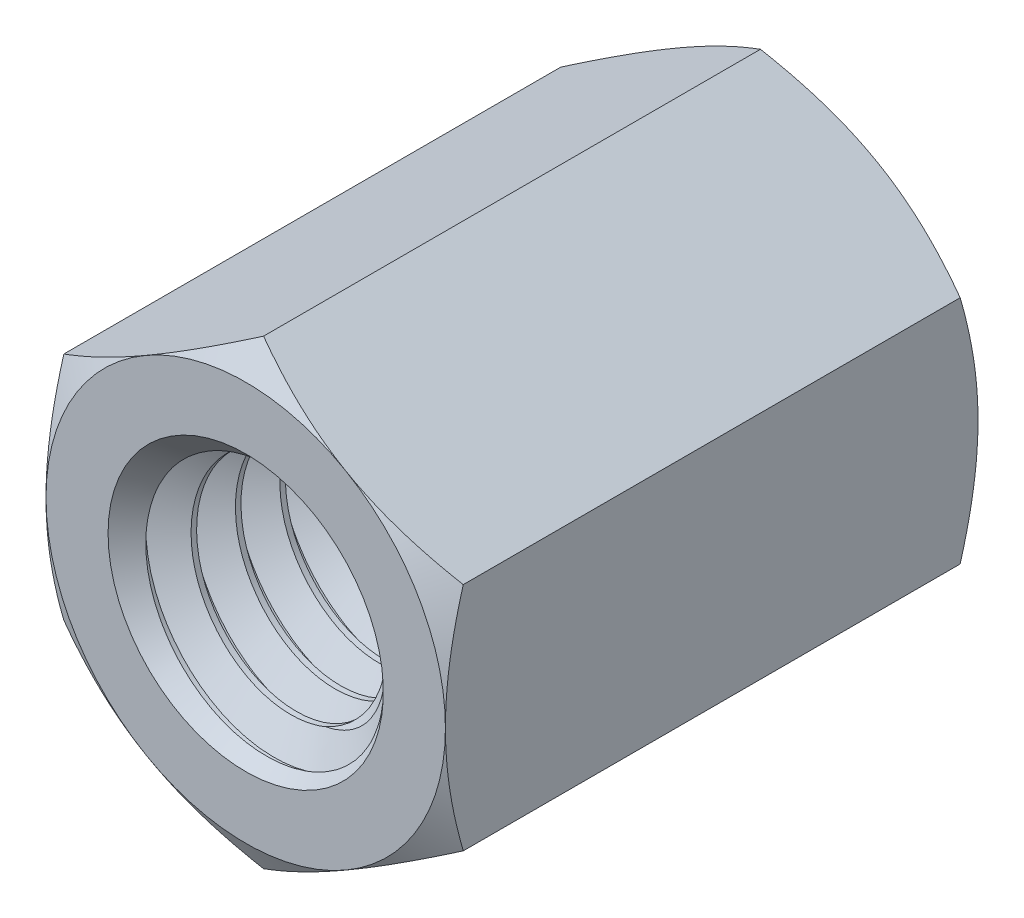
SolidWorks part; units mm, degrees
ref_plane "Front Plane" through (0, 0, 0) normal (0, 0, 1) x (1, 0, 0)
ref_plane "Top Plane" through (0, 0, 0) normal (0, 1, 0) x (1, 0, 0)
ref_plane "Right Plane" through (0, 0, 0) normal (1, 0, 0) x (0, 0, -1)
sketch "Sketch3" plane through (0, 0, 0) normal (1, 0, 0) x (0, 0, -1)
  line L0 (-3, 0) -> (3, 0) construction
  line L1 (0, 2.25) -> (0, -2.25) construction
  line L2 (-3, 1.5) -> (-3, -1.5) construction
  point P2 (-1.8, 0)
  point P3 (1.8, 0)
  dimension "Length" = 6
  dimension "Min Thread Length" = 4.8
  dimension "D1" = 4.8
  dimension "Thread Dia" = 3
  dimension "Hex" = 4.5
sketch "Sketch1" plane through (0, 0, 0) normal (0, 0, 1) x (1, 0, 0)
  line L1 (0, 2.5981) -> (-2.25, 1.299)
  line L2 (-2.25, 1.299) -> (-2.25, -1.299)
  line L3 (-2.25, -1.299) -> (0, -2.5981)
  line L4 (0, -2.5981) -> (2.25, -1.299)
  line L5 (2.25, -1.299) -> (2.25, 1.299)
  line L6 (2.25, 1.299) -> (0, 2.5981)
  circle A0 centre (0, 0) radius 2.25 construction
  circle A1 centre (0, 0) radius 1.5
extrude "Extrude1" add sketch "Sketch1" along normal up to vertex (3 mm away) and the other way up to vertex (3 mm away) up to point (0, 0, 3) other way up to point (0, 0, -3)
sketch "Sketch11" plane through (0, 0, -3) normal (0, 0, -1) x (-1, 0, 0)
  circle A0 centre (0, 0) radius 1.5 construction
  circle A1 centre (0, 0) radius 1.5
curve "Helix/Spiral1" pitch 0.5 height 6.5 radius 1.5 centre (0, 0, -3) axis (0, 0, 1) start towards (0, 1, 0) parameters "Pitch"=0.5
sketch "Sketch12" plane through (0, 0, 0) normal (1, 0, 0) x (0, 0, -1)
  line L0 (3.4375, 1.5) -> (3, 1.5)
  line L1 (3.4375, 1.5) -> (3.25, 1.1752)
  line L2 (3.25, 1.1752) -> (3.1875, 1.1752)
  line L3 (3.1875, 1.1752) -> (3, 1.5)
  line L4 (3.2187, 1.1752) -> (3.2187, 1.5) construction
  line L5 (3.3438, 1.3376) -> (3.0938, 1.3376) construction
  dimension "D1" = 0.0625
  dimension "D2" = 0.25
  dimension "D3" = 60
sweep "Sweep1" add profiles "Sketch12" path "Helix/Spiral1"
sketch "Sketch6" plane through (0, 0, -3) normal (0, 0, -1) x (-1, 0, 0)
  line L6 (0, 2.5981) -> (-2.25, 1.299)
  line L7 (-2.25, 1.299) -> (-2.25, -1.299)
  line L8 (-2.25, -1.299) -> (0, -2.5981)
  line L9 (0, -2.5981) -> (2.25, -1.299)
  line L10 (2.25, -1.299) -> (2.25, 1.299)
  line L11 (2.25, 1.299) -> (0, 2.5981)
  line L12 (0, 2.5981) -> (-2.25, 1.299)
  line L13 (-2.25, 1.299) -> (-2.25, -1.299)
  line L14 (-2.25, -1.299) -> (0, -2.5981)
  line L15 (0, -2.5981) -> (2.25, -1.299)
  line L16 (2.25, -1.299) -> (2.25, 1.299)
  line L17 (2.25, 1.299) -> (0, 2.5981)
  dimension "D1" = 0
extrude "Extrude2" cut sketch "Sketch6" along normal through all
sketch "Sketch7" plane through (0, 0, -3) normal (0, 0, -1) x (-1, 0, 0)
  circle A2 centre (0, 0) radius 1.5508
  circle A3 centre (0, 0) radius 1.5508
  dimension "D1" = 0.0508
extrude "Extrude3" cut sketch "Sketch7" against normal through all draft 43
sketch "Sketch8" plane through (0, 0, -3) normal (0, 0, -1) x (-1, 0, 0)
  circle A0 centre (0, 0) radius 2.25 construction
  circle A1 centre (0, 0) radius 2.25
extrude "Extrude4" cut sketch "Sketch8" against normal through all draft 60 flip side to cut
mirror "Mirror1" about plane through (0, 0, 0) normal (0, 0, 1) of "Extrude2", "Extrude3", "Extrude4"
sketch "Sketch9" [suppressed] plane through (0, 0, 0) normal (1, 0, 0) x (0, 0, -1)
  line L1 (-1.2, 1.1353) -> (1.2, 1.1353)
  line L2 (-1.2, 1.1353) -> (-1.2, 0)
  line L3 (-1.2, 0) -> (1.2, 0)
  line L4 (1.2, 1.1353) -> (1.2, 0)
  line L7 (-6, 0) -> (6, 0) construction
revolve "Revolve" [suppressed] add sketch "Sketch9" angle 360 about L0
sketch "Sketch10" [suppressed] plane through (0, 0, 0) normal (1, 0, 0) x (0, 0, -1)
  line L0 (6, 1.25) -> (1.2, 1.25)
  line L1 (-6, 1.25) -> (-1.2, 1.25)
  line L2 (1.2, 1.25) -> (1.2, -1.25)
  line L3 (-6, -1.25) -> (-1.2, -1.25)
  line L4 (-1.2, 1.25) -> (-1.2, -1.25)
  line L5 (1.2, -1.25) -> (6, -1.25)
equation "\"D1@Sketch3\" = \"Min Thread Length@Sketch3\""
equation "\"D3@Helix/Spiral1\" = \"Length@Sketch3\"+\"Pitch@Helix/Spiral1\""
equation "\"D1@Sketch12\" = \"Pitch@Helix/Spiral1\"*.125"
equation "\"D2@Sketch12\" = \"Pitch@Helix/Spiral1\"*.5"
